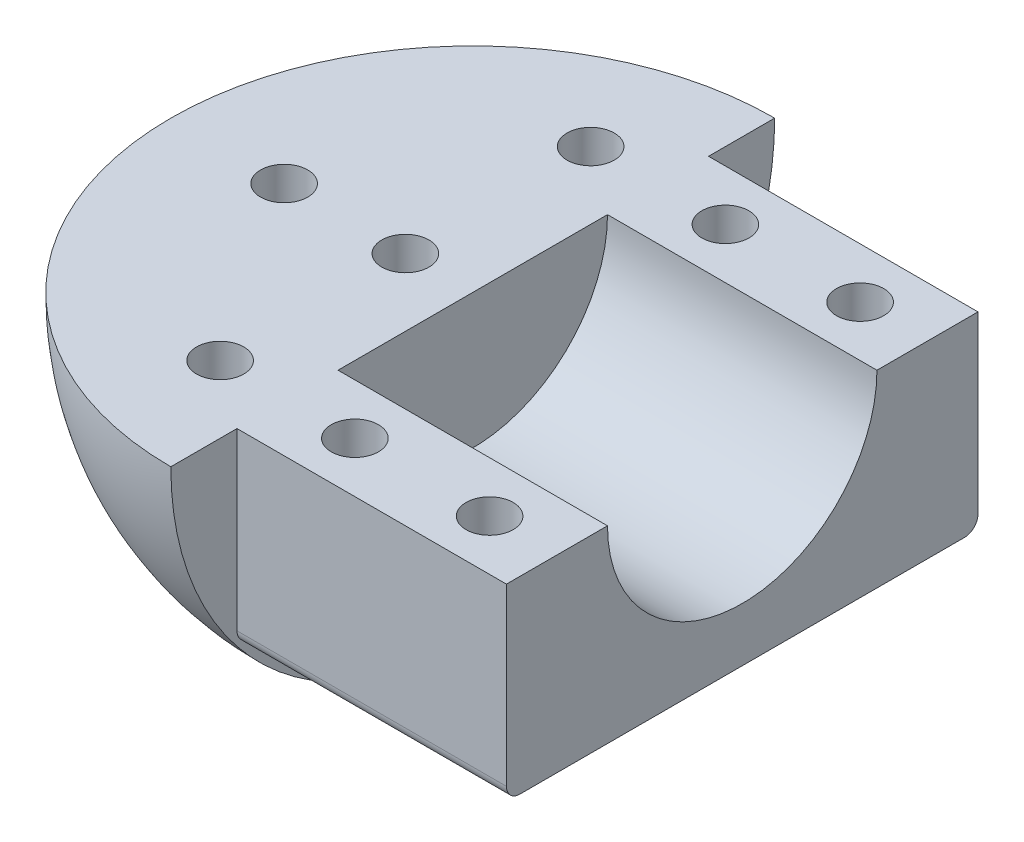
SolidWorks part; units mm, degrees
material "PEI"
ref_plane "Front Plane" through (0, 0, 0) normal (0, 0, 1) x (1, 0, 0)
ref_plane "Top Plane" through (0, 0, 0) normal (0, 1, 0) x (1, 0, 0)
ref_plane "Right Plane" through (0, 0, 0) normal (1, 0, 0) x (0, 0, -1)
sketch "Sketch1" plane through (0, 0, 0) normal (0, 1, 0) x (1, 0, 0)
  line L1 (-20, 17.5) -> (20, 17.5)
  line L2 (-20, 17.5) -> (-20, -17.5)
  line L3 (-20, -17.5) -> (20, -17.5)
  line L4 (20, 17.5) -> (20, -17.5)
  line L5 (-20, 17.5) -> (20, -17.5) construction
  line L6 (-20, -17.5) -> (20, 17.5) construction
  circle A0 centre (0, 0) radius 17.5
  point P0 (0, 0)
  dimension "D1" = 35
  dimension "D2" = 40
extrude "Boss-Extrude1" add sketch "Sketch1" along normal blind 14 and the other way blind 14 contours A0 | A0 L3 L4 L1 region at (10, 0, -17.0969) region at (0, 0, 0)
sketch "Sketch7" plane through (0, 14, 0) normal (0, 1, 0) x (1, 0, 0)
  line L0 (0, 17.5) -> (0, -17.5)
  line L1 (0, -17.5) -> (-23.0726, -17.5)
  line L2 (-23.0726, -17.5) -> (-23.0726, 17.5)
  line L3 (-23.0726, 17.5) -> (0, 17.5)
  arc A0 (0, 17.5) -> (0, -17.5) centre (0, 0) ccw construction
extrude "Cut-Extrude6" cut sketch "Sketch7" against normal blind 120
sketch "Sketch10" plane through (0, 0, 0) normal (1, 0, 0) x (0, 0, -1)
  line L0 (-22.4109, 0) -> (22.4109, 0)
  arc A0 (-22.4109, 0) -> (22.4109, 0) centre (0, 0) ccw
  point P3 (0, 0)
revolve "Revolve1" add sketch "Sketch10" angle 180 about L0
sketch "Sketch3" plane through (20, 0, 0) normal (1, 0, 0) x (0, 0, -1)
  circle A0 centre (0, 0) radius 10
  dimension "D1" = 20
extrude "Cut-Extrude1" cut sketch "Sketch3" against normal blind 20
sketch "Sketch4" plane through (20, 0, 0) normal (1, 0, 0) x (0, 0, -1)
  line L0 (-29.4883, 0) -> (29.964, 0)
  line L1 (29.964, 0) -> (3.9384, 60.1732)
  line L2 (3.9384, 60.1732) -> (-29.4883, 0)
extrude "Cut-Extrude3" cut sketch "Sketch4" against normal blind 64
sketch "Sketch5" plane through (0, 0, 0) normal (0, 1, 0) x (1, 0, 0)
  line L0 (20, 13.75) -> (-5, 13.75) construction
  line L1 (20, 10) -> (20, 17.5) construction
  line L2 (-5, 13.75) -> (-5, -13.75) construction
  line L3 (-5, -13.75) -> (20, -13.75) construction
  line L4 (20, -17.5) -> (20, -10) construction
  line L5 (-14, 0) -> (0, 0) construction
  circle A0 centre (15, 13.75) radius 1.75
  circle A1 centre (5, 13.75) radius 1.75
  circle A2 centre (-5, 13.75) radius 1.75
  circle A3 centre (-5, 0) radius 1.75
  circle A4 centre (-14, 0) radius 1.75
  circle A5 centre (15, -13.75) radius 1.75
  circle A6 centre (5, -13.75) radius 1.75
  circle A7 centre (-5, -13.75) radius 1.75
  dimension "D1" = 3.5
  dimension "D2" = 5
  dimension "D3" = 10
  dimension "D4" = 10
  dimension "D5" = 14
extrude "Cut-Extrude4" cut sketch "Sketch5" against normal blind 39
ref_plane "Plane2" through (0, -24, 0) normal (0, -1, 0) x (-1, 0, 0)
sketch "Sketch6" plane through (0, -24, 0) normal (0, -1, 0) x (1, 0, 0)
  circle A0 centre (-5, 13.75) radius 3.25
  circle A1 centre (5, 13.75) radius 3.25
  circle A2 centre (15, 13.75) radius 3.25
  circle A3 centre (-14, 0) radius 3.25
  circle A4 centre (-5, 0) radius 3.25
  circle A5 centre (-5, -13.75) radius 3.25
  circle A6 centre (5, -13.75) radius 3.25
  circle A7 centre (15, -13.75) radius 3.25
  dimension "D1" = 6.5
extrude "Cut-Extrude5" cut sketch "Sketch6" against normal blind 11.5
fillet "Fillet2" radius 1 2 edges at (10, -14, -17.5) (10, -14, 17.5)
